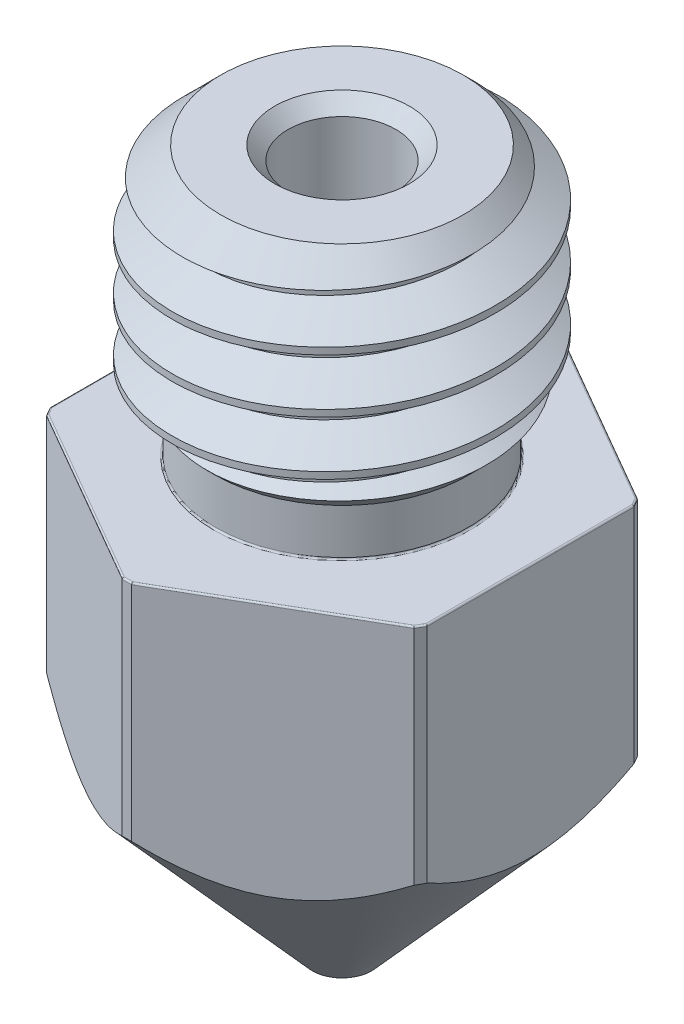
SolidWorks part; units mm, degrees
note: '?' marks a value the reader was unsure of.
ref_plane "Front" through (0, 0, 0) normal (0, 0, 1) x (1, 0, 0)
ref_plane "Top" through (0, 0, 0) normal (0, 1, 0) x (1, 0, 0)
ref_plane "Right" through (0, 0, 0) normal (1, 0, 0) x (0, 0, -1)
sketch "Sketch1" plane through (0, 0, 0) normal (0, 0, 1) x (1, 0, 0)
  line L0 (0, 5) -> (0, -8) construction
  line L1 (-3, 5) -> (3, 5) construction
  line L2 (-3.5, 0) -> (3.5, 0) construction
  line L3 (-0.4, -8) -> (0.4, -8) construction
  line L4 (-0.6362, -8) -> (0.6362, -8) construction
  line L5 (0.4, -7.2) -> (0.4, -8) construction
  line L6 (0.4, -7.2) -> (1, -6.1608) construction
  line L7 (1, -6.1608) -> (-1, -6.1608) construction
  line L8 (-1, -6.1608) -> (-0.4, -7.2) construction
  line L9 (-0.4, -7.2) -> (-0.4, -8) construction
  point P2 (0, 0)
  point P3 (0, -4.1)
  point P7 (0, 5)
  point P10 (0, 0)
  point P13 (0, -8)
  point P16 (0, -8)
  point P21 (3, 3)
  point P22 (3.5, -4.1)
  dimension "D1" = 0.2362
  dimension "D2" = 60
  dimension "D3" = 2
sketch "Sketch3" plane through (0, 0, 0) normal (0, 1, 0) x (1, 0, 0)
  line L0 (-0.4, 0) -> (0.4, 0) construction
  line L1 (0, 4.0415) -> (-3.5, 2.0207)
  line L2 (-3.5, 2.0207) -> (-3.5, -2.0207)
  line L3 (-3.5, -2.0207) -> (0, -4.0415)
  line L4 (0, -4.0415) -> (3.5, -2.0207)
  line L5 (3.5, -2.0207) -> (3.5, 2.0207)
  line L6 (3.5, 2.0207) -> (0, 4.0415)
  circle A0 centre (0, 0) radius 3.5 construction
extrude "Boss-Extrude1" add sketch "Sketch3" against normal up to vertex (8 mm away) up to point (0, -8, 0)
sketch "Sketch13" plane through (0, 0, 0) normal (0, 1, 0) x (1, 0, 0)
  line L0 (-3.5, -2.0207) -> (3.5, 2.0207) construction
ref_plane "Plane1" through (0, 0, 0) normal (0.5, 0, 0.866) x (0.866, 0, -0.5)
sketch "Sketch4" plane through (0, 0, 0) normal (0.5, 0, 0.866) x (0.866, 0, -0.5)
  line L0 (0.551, -8) -> (4.0415, -4.1)
  line L2 (4.0415, -8) -> (4.0415, 0) construction
  line L4 (4.0415, -4.1) -> (4.0415, -8)
  line L5 (4.0415, -8) -> (0.551, -8)
  line L6 (0, 5) -> (0, -8) construction
  line L7 (0, 5) -> (0, -8) construction
revolve "Cut-Revolve1" cut sketch "Sketch4" angle 360 about L7
sketch "Sketch5" plane through (0, 0, 0) normal (0, 1, 0) x (1, 0, 0)
  circle A0 centre (0, 0) radius 3
extrude "Boss-Extrude2" add sketch "Sketch5" along normal up to vertex (5 mm away) separate body up to point (0, 5, 0)
sketch "Sketch9" plane through (0, 0, 0) normal (0, 0, 1) x (1, 0, 0)
  line L0 (1, -6.1608) -> (1, 5)
  line L1 (-3, 5) -> (3, 5) construction
  line L2 (1, 5) -> (0, 5)
  line L3 (0, 5) -> (0, -8)
  line L4 (0, -8) -> (0.4, -8)
  line L5 (0.4, -7.2) -> (0.4, -8) construction
  line L6 (0.4, -7.2) -> (1, -6.1608) construction
  line L7 (0.4, -7.2) -> (0.4, -8)
  line L8 (0.4, -7.2) -> (1, -6.1608)
revolve "Cut-Revolve3" cut sketch "Sketch9" angle 360 about L3
sketch "Sketch10" plane through (0, 0, 0) normal (0, 1, 0) x (1, 0, 0)
  circle A0 centre (0, 0) radius 4.0415 construction
  circle A1 centre (0, 0) radius 3.9915
  dimension "D1" = 0.05
extrude "Cut-Extrude1" cut sketch "Sketch10" against normal through all flip side to cut
sketch "Sketch12" plane through (0, 0, 0) normal (0, 0, 1) x (1, 0, 0)
  line L0 (0, 0) -> (0, 5) construction
  line L1 (1, 5) -> (-1, 5) construction
  line L2 (0, 5) -> (1.8, 5)
  line L3 (3, 5) -> (-3, 5) construction
  line L4 (1.8, 5) -> (1.8, 4.4807)
  line L5 (1.8, 4.4807) -> (1, 4)
  line L6 (1, 0) -> (1, 5) construction
  line L7 (1, 4) -> (0, 4)
  line L8 (0, 4) -> (0, 5)
  dimension "D1" = 1
  dimension "D2" = 3.6
  dimension "D3" = 31
revolve "Cut-Revolve4" [suppressed] cut sketch "Sketch12" angle 360 about L0
chamfer "Chamfer4" [suppressed] distance 0.25 angle 45
chamfer "Chamfer5" distance 0.25 angle 45 1 edges at (-1, 5, 0)
sketch "Sketch6" plane through (0, 5, 0) normal (0, 1, 0) x (1, 0, 0)
  circle A1 centre (0, 0) radius 3
  circle A2 centre (0, 0) radius 3
  dimension "D1" = 0
curve "Helix/Spiral1" pitch 1 height 6 turns 6 parameters "Pitch"=1
chamfer "Chamfer1" distance 0.75 angle 45 1 edges at (0, 5, 3)
sketch "Sketch7" plane through (0, 0, 0) normal (0, 0, 1) x (1, 0, 0)
  line L0 (3, 5.875) -> (3, 5) construction
  line L1 (3, 5) -> (2.3505, 5.375)
  line L2 (2.3505, 5.5) -> (3, 5.875)
  line L3 (3, 5.4375) -> (2.3505, 5.4375) construction
  line L4 (2.3505, 5.5) -> (2.3505, 5.375)
  line L5 (3, 5) -> (3.127, 4.9267)
  line L6 (3.127, 4.9267) -> (3.127, 5.9483)
  line L7 (3.127, 5.9483) -> (3, 5.875)
  line L8 (2.6752, 5.6875) -> (2.6752, 5.1875) construction
  dimension "D1" = 60
  dimension "D2" = 0.127
  dimension "D3" = 0.125
  dimension "D4" = 0.5
sweep "Cut-Sweep1" cut profiles "Sketch7" path "Helix/Spiral1" align with end faces yes
sketch "Sketch8" plane through (0, 0, 0) normal (0, 0, 1) x (1, 0, 0)
  line L0 (2.3505, 0) -> (3, 0)
  line L1 (-3.5, 0) -> (3.5, 0) construction
  line L2 (3, 0) -> (3, 1.5167)
  line L3 (3, 1.5167) -> (2.3505, 0.8671)
  line L4 (2.3505, 0.8671) -> (2.3505, 0)
  line L6 (3, 5.875) -> (3, 5) construction
  line L7 (0, 5) -> (0, -8) construction
  line L8 (0, 5) -> (0, -8) construction
  dimension "D1" = 45
  dimension "D2" = 0.8671
revolve "Cut-Revolve2" cut sketch "Sketch8" angle 360 about L8
combine bodies "Combine1" operation type add bodies to combine 113 118
fillet "Fillet1" radius 0.03 13 edges at (0, 0, 2.3505) (-3.4567, 0, 1.9957) (-3.5, 0, 0) (-3.4567, 0, -1.9957) (-1.75, 0, -3.0311) (0, 0, -3.9915) (1.75, 0, -3.0311) (3.4567, 0, -1.9957) (3.5, 0, 0) (3.4567, 0, 1.9957) (1.75, 0, 3.0311) (0, 0, 3.9915) (-1.75, 0, 3.0311)
ref_axis "Axis1" through (0, 5, 0) along (0, -1, 0)?
ref_plane "Contact Plane 1" through (0, -8, 0) normal (0, -1, 0) x (-1, 0, 0)
ref_plane "Contact Plane 2" through (0, 0, 0) normal (0, 1, 0) x (1, 0, 0)
ref_plane "Contact Plane 3" through (0, 5, 0) normal (0, 1, 0) x (1, 0, 0)
equation "\"D3@Sketch7\"=\"Pitch@Helix/Spiral1\"/8"
equation "\"D4@Sketch7\"=\"Pitch@Helix/Spiral1\"/2"
equation "\"D1@Chamfer1\"=\"Pitch@Helix/Spiral1\"*.75"
equation "\"D3@Helix/Spiral1\"=\"Thread Length@Sketch1\"+\"Pitch@Helix/Spiral1\""
equation "\"D3@Sketch1\"=\"Pitch@Helix/Spiral1\"*2"
